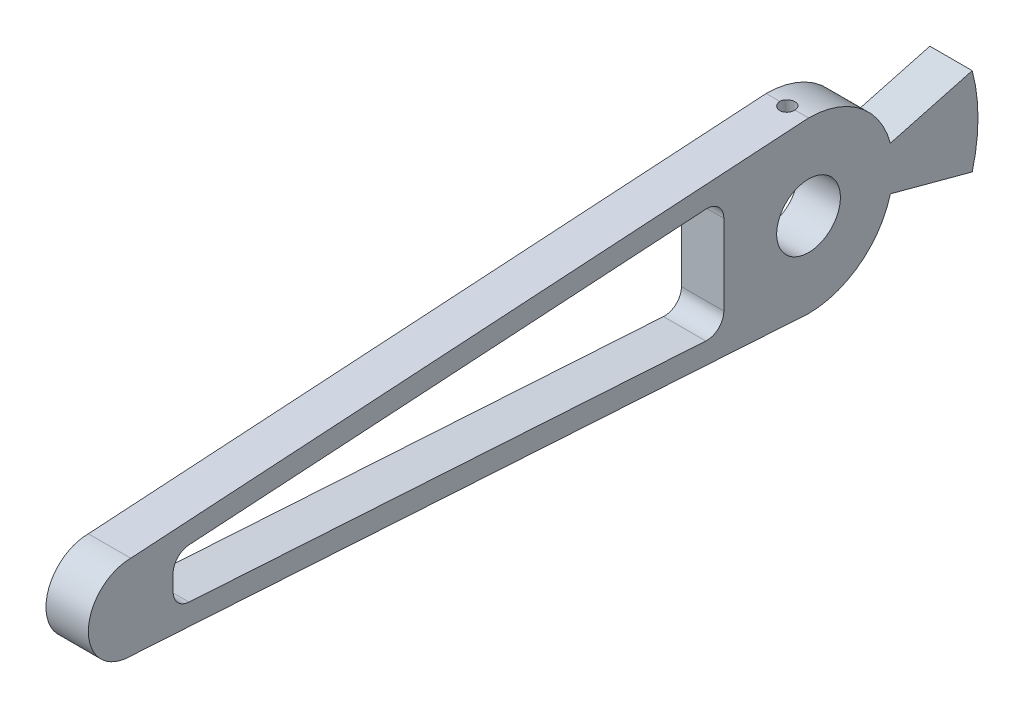
SolidWorks part; units mm, degrees
material "6061-T6 (SS)"
ref_plane "Front Plane" through (0, 0, 0) normal (0, 0, 1) x (1, 0, 0)
ref_plane "Top Plane" through (0, 0, 0) normal (0, 1, 0) x (1, 0, 0)
ref_plane "Right Plane" through (0, 0, 0) normal (1, 0, 0) x (0, 0, -1)
sketch "Sketch1" plane through (0, 0, 0) normal (1, 0, 0) x (0, 0, -1)
  line L0 (0, 12.7) -> (0, -12.7) construction
  line L1 (0, 0) -> (-101.6, 0) construction
  line L2 (0, 12.7) -> (-101.6, 6.35)
  line L3 (0, -12.7) -> (-101.6, -6.35)
  line L4 (-12.7, -6.0213) -> (-12.7, 6.0213)
  line L5 (-95.25, -1.1795) -> (-95.25, 1.1795)
  line L6 (-15.3984, 8.5564) -> (-92.8684, 3.7145)
  line L7 (-92.8684, -3.7145) -> (-15.3984, -8.5564)
  line L8 (0, 0) -> (24.5345, 6.574)
  line L9 (0, 0) -> (24.5345, -6.574)
  line L10 (0, 0) -> (25.4, 0) construction
  arc A0 (-1.5813, -12.6012) -> (-1.5813, 12.6012) centre (0, 0) ccw
  arc A1 (-101.6, 6.35) -> (-101.6, -6.35) centre (-101.6, 0) ccw
  arc A2 (-12.7, 6.0213) -> (-15.3984, 8.5564) centre (-15.24, 6.0213) ccw
  arc A3 (-12.7, -6.0213) -> (-15.3984, -8.5564) centre (-15.24, -6.0213) cw
  arc A4 (-92.8684, -3.7145) -> (-95.25, -1.1795) centre (-92.71, -1.1795) cw
  arc A5 (-92.8684, 3.7145) -> (-95.25, 1.1795) centre (-92.71, 1.1795) ccw
  circle A6 centre (0, 0) radius 4.7752
  circle A7 centre (0, 0) radius 25.4
  dimension "D1" = 25.4
  dimension "D3" = 12.7
  dimension "D6" = 2.54
  dimension "D7" = 2.54
  dimension "D8" = 2.54
  dimension "D9" = 2.54
  dimension "D10" = 9.5504
  dimension "D11" = 50.8
  dimension "D2" = 101.6
  dimension "D4" = 3.175
  dimension "D5" = 3.175
  dimension "D12" = 15
  dimension "D13" = 15
extrude "Boss-Extrude1" add sketch "Sketch1" along normal blind 6.35 contours L2 A1 L3 A0 A6 A5 L6 A2 L4 A3 L7 A4 L5 | A7 L2 A1 L3 L7 A4 L5 A5 L6 | A6 L9 A0 L8 | L9 A7 L8 A0 region at (0, 9.7236, -7.4612) region at (0, 0, -9.2303) region at (0, 0, -19.5307) region at (0, 10.0038, 24.3029)
hole_wizard "#4-40 Tapped Hole1" positions "3DSketch1" profile "Sketch2" tap size "#4-40" standard "ANSI Inch" end condition up to next
sketch3d "3DSketch1"
  line L0 (6.35, 12.7, 0) -> (0, 12.7, 0) construction
  point P1 (3.175, 12.7, 0)
sketch "Sketch2" plane through (3.175, 12.7, 0) normal (1, 0, 0) x (0, -0.0624, 0.9981)
  line L0 (0, 0) -> (0, 7.9662)
  line L1 (0, 7.9662) -> (1.1303, 7.9662)
  line L2 (1.1303, 7.9662) -> (1.1303, 0)
  line L5 (1.1303, 0) -> (0, 0)
  line L11 (0, -6.35) -> (0, 107.95) construction
  dimension "Thru Tap Drill Dia." = 2.2606
  dimension "Thru Tap Drill Depth" = 7.9662
cosmetic thread "Hole Thread1" parameters "D2"=2.8448
